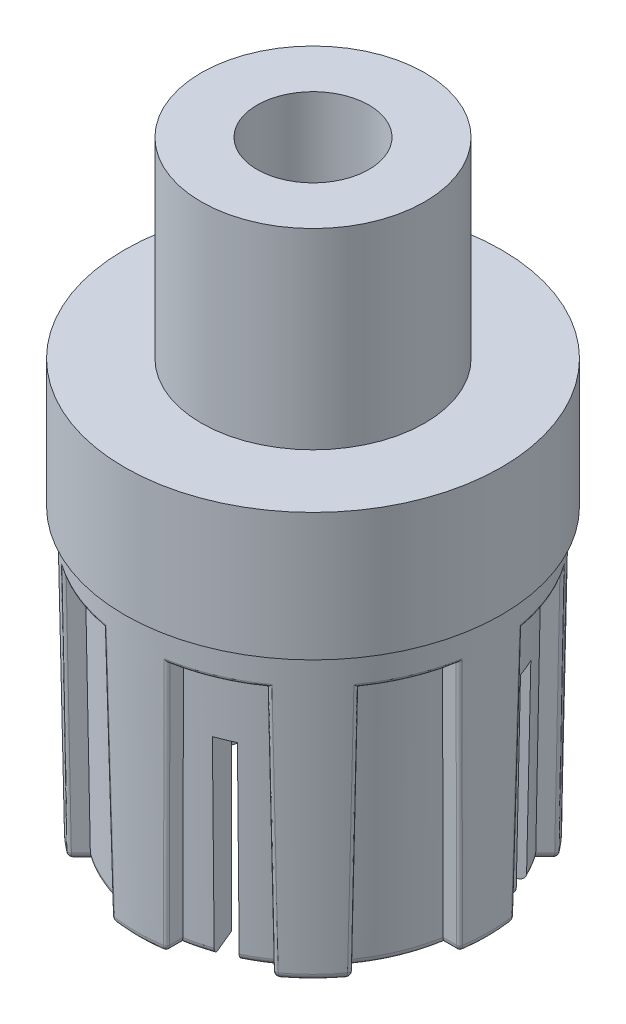
SolidWorks part; units mm, degrees
ref_plane "Спереди" through (0, 0, 0) normal (0, 0, 1) x (1, 0, 0)
ref_plane "Сверху" through (0, 0, 0) normal (0, 1, 0) x (1, 0, 0)
ref_plane "Справа" through (0, 0, 0) normal (1, 0, 0) x (0, 0, -1)
other "Configuration Table"
sketch "Эскиз1" plane through (0, 0, 0) normal (0, 1, 0) x (1, 0, 0)
  circle A5 centre (0, 0) radius 5.5
  dimension "D1" = 11
extrude "Бобышка-Вытянуть1" add sketch "Эскиз1" along normal blind 9 draft 1 draft outward yes
sketch "Эскиз2" plane through (0, 9, 0) normal (0, 1, 0) x (1, 0, 0)
  circle A1 centre (0, 0) radius 5.9
  dimension "D1" = 11.8
extrude "Бобышка-Вытянуть2" add sketch "Эскиз2" along normal blind 4
chamfer "Фаска1" [suppressed] distance 1 angle 45
fillet "Скругление1" [suppressed] radius 0.5
sketch "Эскиз3" plane through (0, 13, 0) normal (0, 1, 0) x (1, 0, 0)
  circle A0 centre (0, 0) radius 2.05
  circle A1 centre (0, 0) radius 3.5
  dimension "D1" = 7
extrude "Бобышка-Вытянуть3" [suppressed] add sketch "Эскиз3" along normal blind 7
chamfer "Фаска2" [suppressed] distance 0.3 angle 45
sketch "Эскиз4" plane through (0, 13, 0) normal (0, 1, 0) x (1, 0, 0)
  circle A0 centre (0, 0) radius 3.5
  dimension "D1" = 7
extrude "Бобышка-Вытянуть4" add sketch "Эскиз4" along normal blind 6
chamfer "Фаска3" [suppressed] distance 0.3 angle 45
sketch "Эскиз5" plane through (0, 13, 0) normal (0, 1, 0) x (1, 0, 0)
  circle A0 centre (0, 0) radius 7.75
  dimension "D1" = 15.5
sketch "Эскиз6" plane through (0, 0, 0) normal (0, -1, 0) x (1, 0, 0)
  line L0 (0, 0) -> (0, 8.8078) construction
  line L1 (-0.85, 5.707) -> (-0.85, 4.9272)
  line L2 (3.433, 4.6376) -> (2.8815, 4.0862)
  line L3 (0.85, 4.9272) -> (0.85, 5.707)
  line L4 (4.0841, 2.8845) -> (4.6355, 3.4359)
  line L5 (5.707, 0.85) -> (4.9272, 0.85)
  line L6 (4.9272, -0.85) -> (5.707, -0.85)
  line L7 (4.6339, -3.438) -> (4.0826, -2.8866)
  line L8 (2.8794, -4.0876) -> (3.4309, -4.6391)
  line L9 (0.8414, -5.7083) -> (0.8414, -4.9287)
  line L10 (-0.8586, -4.9257) -> (-0.8586, -5.7058)
  line L11 (-3.4429, -4.6303) -> (-2.8917, -4.079)
  line L12 (-4.0912, -2.8744) -> (-4.6428, -3.426)
  line L13 (-5.7083, -0.8414) -> (-4.9287, -0.8414)
  line L14 (-4.9257, 0.8586) -> (-5.7058, 0.8586)
  line L15 (-4.6339, 3.438) -> (-4.0826, 2.8866)
  line L16 (-2.8794, 4.0876) -> (-3.4309, 4.6391)
  arc A1 (-0.85, 4.9272) -> (-2.8794, 4.0876) centre (0, 0) ccw
  arc A2 (-3.4309, 4.6391) -> (-4.6339, 3.438) centre (0, 0) ccw
  arc A3 (0.85, 5.707) -> (-0.85, 5.707) centre (0, 0) ccw
  arc A4 (2.8815, 4.0862) -> (0.85, 4.9272) centre (0, 0) ccw
  arc A5 (4.6355, 3.4359) -> (3.433, 4.6376) centre (0, 0) ccw
  arc A6 (4.9272, 0.85) -> (4.0841, 2.8845) centre (0, 0) ccw
  arc A7 (5.707, -0.85) -> (5.707, 0.85) centre (0, 0) ccw
  arc A8 (4.0826, -2.8866) -> (4.9272, -0.85) centre (0, 0) ccw
  arc A9 (3.4309, -4.6391) -> (4.6339, -3.438) centre (0, 0) ccw
  arc A10 (0.8414, -4.9287) -> (2.8794, -4.0876) centre (0, 0) ccw
  arc A11 (-0.8586, -5.7058) -> (0.8414, -5.7083) centre (0, 0) ccw
  arc A12 (-2.8917, -4.079) -> (-0.8586, -4.9257) centre (0, 0) ccw
  arc A13 (-4.6428, -3.426) -> (-3.4429, -4.6303) centre (0, 0) ccw
  arc A14 (-4.9287, -0.8414) -> (-4.0912, -2.8744) centre (0, 0) ccw
  arc A15 (-5.7058, 0.8586) -> (-5.7083, -0.8414) centre (0, 0) ccw
  arc A16 (-4.0826, 2.8866) -> (-4.9257, 0.8586) centre (0, 0) ccw
  circle A17 centre (0, 0) radius 6.612
  point P42 (-0.0043, 0.0043)
  dimension "D3" = 10
  dimension "D5" = 5.77
  dimension "D1" = 0.85
  dimension "D2" = 0.85
  dimension "D4" = 8
extrude "Вырез-Вытянуть1" cut sketch "Эскиз6" against normal blind 8 draft 1
fillet "Скругление2" radius 0.2 32 edges at (1.9126, 0, 4.6197) (3.0607, 0, 4.2653) (3.8878, 0, 3.8904) (4.2632, 0, 3.0636) (4.6191, 0, 1.9143) (5.1806, 0, 0.85) (5.5, 0, 0) (5.1806, 0, -0.85) (4.6186, 0, -1.9154) (4.2617, 0, -3.0657) (3.886, 0, -3.8922) (3.0586, 0, -4.2668) (1.9073, 0, -4.6219) (0.8414, 0, -5.182) (-0.0087, 0, -5.5) (-0.8586, 0, -5.1791) (-1.9223, 0, -4.6157) (-3.0708, 0, -4.2581) (-3.8965, 0, -3.8816) (-4.2704, 0, -3.0536) (-4.6231, 0, -1.9045) (-5.182, 0, -0.8414) (-5.5, 0, 0.0087) (-5.1791, 0, 0.8586) (-4.6169, 0, 1.9195) (-4.2617, 0, 3.0657) (-3.886, 0, 3.8922) (-3.0586, 0, 4.2668) (-1.9114, 0, 4.6202) (-0.85, 0, 5.1806) (0, 0, 5.5) (0.85, 0, 5.1806)
fillet "Скругление4" radius 0.1 41 edges at (0.823, 0.0939, 5.4107) (-0.823, 0.0939, 5.4107) (-3.2405, 0.0938, 4.4105) (-4.4053, 0.0939, 3.2476) (-5.4094, 0.0938, 0.8316) (-5.4121, 0.0939, -0.8144) (-4.4141, 0.0938, -3.2355) (-3.2525, 0.0939, -4.4017) (-0.8316, 0.0938, -5.4094) (0.8144, 0.0939, -5.4121) (3.2405, 0.0938, -4.4105) (4.4053, 0.0939, -3.2476) (5.4107, 0.0939, -0.823) (5.4107, 0.0939, 0.823) (4.4068, 0.0939, 3.2455) (3.2426, 0.0938, 4.409) (2.1574, 8, 5.2107) (-2.1562, 8, 5.2112) (-5.2078, 8, 2.1643) (-5.214, 8, -2.1492) (-2.1671, 8, -5.2066) (2.1521, 8, -5.2129) (5.2095, 8, -2.1602) (5.21, 8, 2.159) (0, 9, 5.6571)
sketch "Эскиз7" plane through (0, 0, 0) normal (0, -1, 0) x (1, 0, 0)
  circle A0 centre (0, 0) radius 1.75
  dimension "D1" = 3.5
extrude "Вырез-Вытянуть2" cut sketch "Эскиз7" against normal through all
sketch "Эскиз8" plane through (0, 0, 0) normal (0, -1, 0) x (1, 0, 0)
  circle A0 centre (0, 0) radius 4
  dimension "D1" = 8
extrude "Вырез-Вытянуть3" cut sketch "Эскиз8" against normal blind 7
sketch "Эскиз9" plane through (0, 0, 0) normal (0, -1, 0) x (1, 0, 0)
  line L0 (-6.4198, 2.3357) -> (-0.3915, -0.1613)
  line L1 (5.944, -2.7855) -> (6.1732, -2.2323)
  line L2 (6.1732, -2.2323) -> (0.392, 0.1624)
  line L3 (-6.1907, 2.889) -> (-6.4198, 2.3357)
  line L4 (0.7839, 0) -> (12.9407, 0) construction
  line L5 (-0.1624, 0.392) -> (2.2618, 6.2445)
  line L6 (2.2618, 6.2445) -> (2.8162, 6.0149)
  line L7 (2.8162, 6.0149) -> (0.392, 0.1624)
  line L8 (-0.3915, -0.1613) -> (-2.8805, -6.1701)
  line L9 (-2.8805, -6.1701) -> (-2.3261, -6.3997)
  line L10 (-2.3261, -6.3997) -> (0.1628, -0.3909)
  line L11 (-0.1624, 0.392) -> (-6.1907, 2.889)
  line L12 (0.1628, -0.3909) -> (5.944, -2.7855)
  dimension "D1" = 22.5
  dimension "D3" = 0.5988
  dimension "D4" = 0.6
  dimension "D6" = 0.6
extrude "Вырез-Вытянуть4" cut sketch "Эскиз9" against normal blind 6
equation "\"0б9\"=0.846762"
